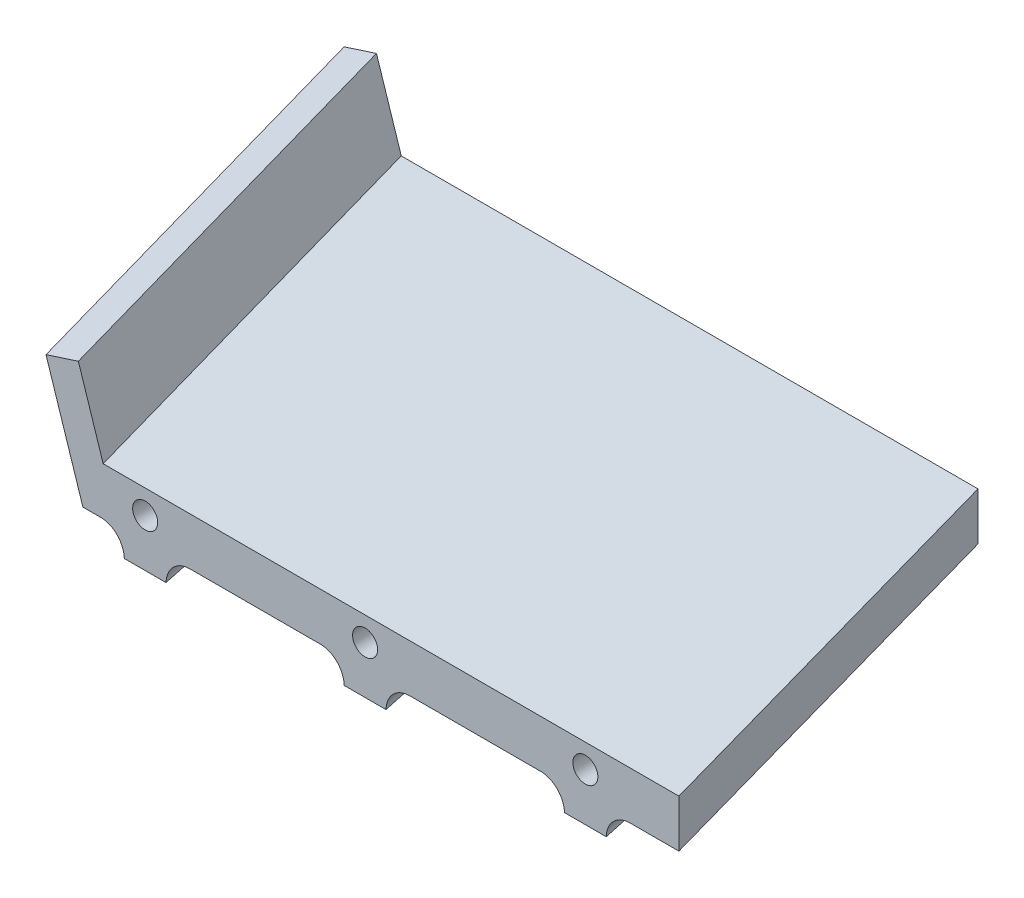
SolidWorks part; units mm, degrees
material "Polybutadiene (PB)"
ref_plane "Plano frontal" through (0, 0, 0) normal (0, 0, 1) x (1, 0, 0)
ref_plane "Plano superior" through (0, 0, 0) normal (0, 1, 0) x (1, 0, 0)
ref_plane "Plano direito" through (0, 0, 0) normal (1, 0, 0) x (0, 0, -1)
sketch "Esboço2" plane through (0, 0, 0) normal (0, 0, 1) x (1, 0, 0)
  line L0 (0, 0) -> (100, 0)
  line L1 (100, 0) -> (100, 8)
  line L2 (100, 8) -> (0, 8)
  line L3 (0, 8) -> (0, 0)
  dimension "D1" = 100
  dimension "D2" = 8
sketch "Esboço3" plane through (0, 0, 0) normal (1, 0, 0) x (0, 0, -1)
  line L0 (0, 0) -> (-55, -14.7372)
  line L1 (0, 0) -> (0, 8) construction
  dimension "D1" = 105
  dimension "D2" = 55
sweep "Varredura1" add profiles "Esboço2" path "Esboço3"
sketch "Esboço4" plane through (0, 0, 0) normal (0, -0.9659, -0.2588) x (1, 0, 0)
  line L0 (0, 0) -> (0, 56.9402)
  line L4 (0, 56.9402) -> (-4.9816, 0)
  line L5 (-4.9816, 0) -> (0, 0)
  dimension "D1" = 5
sketch "Esboço5" plane through (0, 0, 0) normal (-1, 0, 0) x (0, 0, 1)
  line L0 (0, 0) -> (0, 8)
sweep "Varredura2" add profiles "Esboço4" path "Esboço5"
sketch "Esboço6" plane through (0, 0, 0) normal (0, 1, 0) x (1, 0, 0)
  line L1 (100, 0) -> (-4.9816, 0) construction
  line L4 (100, -55) -> (100, 0)
  line L5 (100, -55) -> (95.1881, 0)
  line L6 (95.1881, 0) -> (100, 0)
  dimension "D1" = 5
extrude "Corte-extrusão1" cut sketch "Esboço6" against normal blind 23 and the other way blind 17
sketch "Esboço14" plane through (0, 0, 0) normal (0, 0, 1) x (1, 0, 0)
  line L0 (-4.9816, 0) -> (-16.1167, 34.2702)
  line L1 (-4.9816, 0) -> (-4.9816, 8) construction
  dimension "D1" = 18
hole_wizard "Broca de rosquear para tarraxa de M51" positions "Esboço17" profile "Esboço18" hole size "M5" standard "ISO"
sketch "Esboço17" plane through (0, 0, 55) normal (0, 0, 1) x (1, 0, 0)
  line L0 (0, -10.7372) -> (100, -10.7372) construction
  line L1 (0, -6.7372) -> (0, -14.7372) construction
  line L2 (100, -14.7372) -> (100, -6.7372) construction
  point P0 (10.4489, -10.7372)
  point P2 (47.3489, -10.7372)
  point P4 (84.3067, -10.7372)
  dimension "D1" = 36.9
sketch "Esboço18" plane through (10.4489, -10.7372, 55) normal (1, 0, 0) x (0, -1, 0)
  line L0 (0, 0) -> (0, 16.2618)
  line L1 (0, 16.2618) -> (2.1, 15)
  line L2 (2.1, 15) -> (2.1, 0)
  line L5 (2.1, 0) -> (0, 0)
  line L10 (0, 16.2618) -> (-2.1, 15) construction
  line L11 (0, -6.35) -> (0, 107.95) construction
  dimension "Hole Dia." = 4.2
  dimension "Hole Depth" = 15
  dimension "Drill Angle" = 118
sketch "Esboço19" plane through (0, 0, 55) normal (0, 0, 1) x (1, 0, 0)
  line L0 (80.8067, -14.7372) -> (87.8067, -14.7372)
  line L1 (0, -14.7372) -> (100, -14.7372) construction
  line L2 (87.8067, -14.7372) -> (87.8067, -18.7372)
  line L3 (87.8067, -18.7372) -> (80.8067, -18.7372)
  line L4 (80.8067, -18.7372) -> (80.8067, -14.7372)
  line L5 (43.8489, -14.7372) -> (50.8489, -14.7372)
  line L6 (50.8489, -14.7372) -> (50.8489, -18.7372)
  line L7 (50.8489, -18.7372) -> (43.8489, -18.7372)
  line L8 (43.8489, -18.7372) -> (43.8489, -14.7372)
  line L9 (6.9489, -14.7372) -> (13.9489, -14.7372)
  line L10 (13.9489, -14.7372) -> (13.9489, -18.7372)
  line L11 (13.9489, -18.7372) -> (6.9489, -18.7372)
  line L12 (6.9489, -18.7372) -> (6.9489, -14.7372)
  line L13 (84.3067, -10.7372) -> (84.3067, -14.7372) construction
  line L14 (47.3489, -10.7372) -> (47.3489, -14.7372) construction
  line L15 (10.4489, -10.7372) -> (10.4489, -14.7372) construction
  dimension "D1" = 4
  dimension "D2" = 7
  dimension "D3" = 7
  dimension "D4" = 4
  dimension "D5" = 7
  dimension "D6" = 4
sketch "Esboço20" plane through (0, 0, 0) normal (0, -0.9659, -0.2588) x (1, 0, 0)
  line L0 (6.9489, 56.9402) -> (6.9489, 36.9402)
  dimension "D1" = 20
sweep "Varredura7" add profiles "Esboço19" path "Esboço20"
fillet "Filete1" radius 4 9 edges at (10.4489, -9.5608, 35.6815) (47.3489, -9.5608, 35.6815) (84.3067, -9.5608, 35.6815) (13.9489, -12.149, 45.3407) (6.9489, -12.149, 45.3407) (43.8489, -12.149, 45.3407) (50.8489, -12.149, 45.3407) (80.8067, -12.149, 45.3407) (87.8067, -12.149, 45.3407)
sketch "Esboço15" plane through (0, 0, 0) normal (0, -0.9659, -0.2588) x (1, 0, 0)
  line L0 (-4.9816, 0) -> (0, 56.9402)
  line L1 (0, 56.9402) -> (6, 56.9402)
  line L2 (0, 56.9402) -> (2.9512, 56.9402) construction
  line L3 (6, 56.9402) -> (1.0184, 0)
  line L4 (-4.9816, 0) -> (95.1881, 0) construction
  line L5 (1.0184, 0) -> (-4.9816, 0)
  dimension "D1" = 6
sweep "Varredura6" add profiles "Esboço15" path "Esboço14"
sketch "Esboço16" plane through (-4.5059, -1.464, 0.0158) normal (-0.9511, -0.309, 0.0033) x (0.0032, 0.001, 1)
  line L0 (58.6818, 4.9723) -> (-0.0158, 21.5732)
  line L2 (-0.0158, 1.5394) -> (-0.0158, 37.5732) construction
  line L3 (-0.0158, 21.5732) -> (-0.0158, 37.5732)
  line L4 (-0.0158, 37.5732) -> (58.6818, 20.9723)
  line L5 (58.6818, 20.9723) -> (58.6818, 4.9723)
  dimension "D1" = 16
  dimension "D2" = 61
extrude "Corte-extrusão3" cut sketch "Esboço16" against normal blind 6
